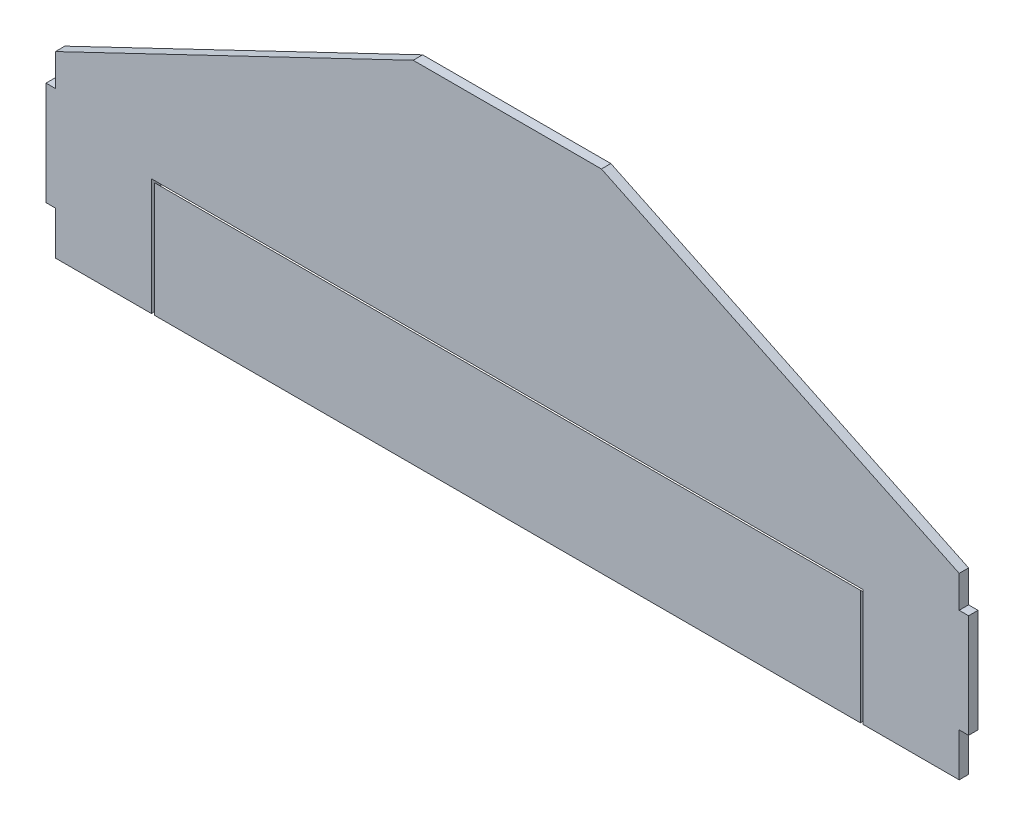
SolidWorks part; units mm, degrees
ref_plane "Ebene vorne" through (0, 0, 0) normal (0, 0, 1) x (1, 0, 0)
ref_plane "Ebene oben" through (0, 0, 0) normal (0, 1, 0) x (1, 0, 0)
ref_plane "Ebene rechts" through (0, 0, 0) normal (1, 0, 0) x (0, 0, -1)
sketch "Skizze1" plane through (0, 0, 0) normal (0, 0, 1) x (1, 0, 0)
  line L0 (0, 0) -> (0, 186) construction
  line L1 (240, 0) -> (-240, 0)
  line L2 (-240, 0) -> (-240, 95)
  line L3 (-240, 95) -> (-50, 186)
  line L4 (-50, 186) -> (50, 186)
  line L5 (240, 0) -> (240, 95)
  line L6 (240, 95) -> (50, 186)
  dimension "D1" = 480
  dimension "D2" = 186
  dimension "D3" = 95
  dimension "D4" = 100
extrude "Grundfläche" add sketch "Skizze1" along normal blind 5
sketch "Skizze3" plane through (0, 0, 5) normal (0, 0, 1) x (1, 0, 0)
  line L0 (0, 0) -> (0, 186) construction
  line L1 (50, 186) -> (-50, 186) construction
  line L2 (240, 0) -> (240, 95) construction
  line L3 (240, 78) -> (245, 78)
  line L4 (240, 78) -> (240, 23)
  line L5 (240, 23) -> (245, 23)
  line L6 (245, 78) -> (245, 23)
  line L7 (-245, 78) -> (-245, 23)
  line L8 (-240, 23) -> (-245, 23)
  line L9 (-240, 78) -> (-240, 23)
  line L10 (-240, 78) -> (-245, 78)
  dimension "D1" = 5
  dimension "D2" = 55
  dimension "D3" = 17
extrude "ZapfenSeitenleitwerk" add sketch "Skizze3" against normal up to surface (5 mm away) up to face at (0, 93.6667, 0)
sketch "Skizze4" plane through (0, 0, 5) normal (0, 0, 1) x (1, 0, 0)
  line L0 (0, 0) -> (0, 62) construction
  line L1 (187.5, 62) -> (-187.5, 62) construction
  line L2 (-187.5, 61) -> (-187.5, 0) construction
  line L3 (-240, 0) -> (240, 0) construction
  line L4 (187.5, 62) -> (187.5, 0) construction
  line L5 (-187.5, 0) -> (-189, 0)
  line L6 (-187.5, 0) -> (-187.5, 61)
  line L7 (-187.5, 62) -> (-189, 62)
  line L8 (-189, 0) -> (-189, 62)
  line L9 (189, 0) -> (189, 62)
  line L10 (187.5, 62) -> (189, 62)
  line L11 (187.5, 0) -> (187.5, 61)
  line L12 (187.5, 0) -> (189, 0)
  line L14 (-187.5, 62) -> (187.5, 62)
  line L16 (-187.5, 61) -> (187.5, 61)
  dimension "D1" = 1.5
  dimension "D2" = 62
  dimension "D3" = 375
  dimension "D4" = 1
extrude "Höhenleitwerk" cut sketch "Skizze4" against normal through all
chamfer "Fase1" distance 5 angle 45 1 edges at (0, 61, 0)
